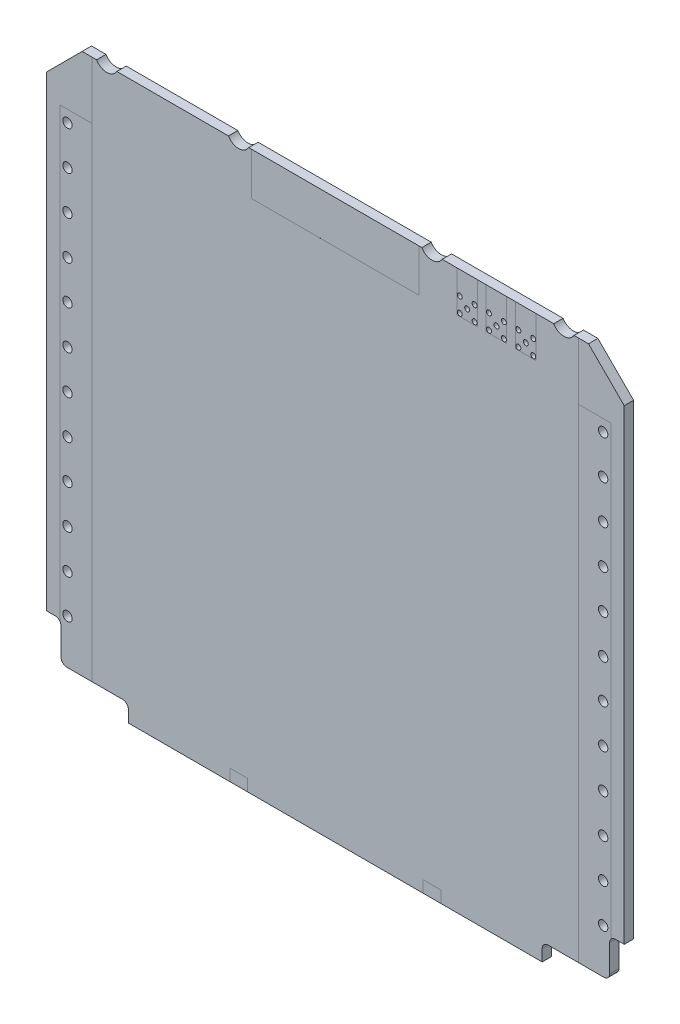
SolidWorks part; units mm, degrees
material "FR4_stuffedProtoboard"
ref_plane "Front Plane" through (0, 0, 0) normal (0, 0, 1) x (1, 0, 0)
ref_plane "Top Plane" through (0, 0, 0) normal (0, 1, 0) x (1, 0, 0)
ref_plane "Right Plane" through (0, 0, 0) normal (1, 0, 0) x (0, 0, -1)
ref_plane "Plane4" through (0, 0, -0.0125) normal (0, 0, -1) x (-1, 0, 0)
sketch "Sketch1" plane through (0, 0, -0.0125) normal (0, 0, -1) x (-1, 0, 0)
  line L4 (49.3, -50) -> (49.3, 45.3)
  line L6 (49.3, 45.3) -> (-49.3, 45.3)
  line L12 (-49.3, 45.3) -> (-49.3, -50)
  line L17 (-49.3, -50) -> (49.3, -50)
  line L18 (0, -50) -> (0, 45.3) construction
  dimension "D7" = 95.3
  dimension "D1" = 98.6
  dimension "D34" = 50
extrude "basicSize" add sketch "Sketch1" against normal blind 1.6
chamfer "Chamfer1" distance 6.1 angle 45 2 edges at (49.3, 45.3, 0.7875) (-49.3, 45.3, 0.7875)
sketch "Sketch4" plane through (0, 0, 1.5875) normal (0, 0, 1) x (1, 0, 0)
  line L1 (37.2679, 45.3) -> (40.7321, 45.3)
  line L7 (-43.2, 45.3) -> (43.2, 45.3) construction
  line L8 (49.3, 39.2) -> (49.3, -50) construction
  arc A0 (40.7321, 45.3) -> (37.2679, 45.3) centre (39, 46.3) cw
  point P5 (39, 44.3)
  dimension "D1" = 2
  dimension "D3" = 10.3
  dimension "D2" = 1
extrude "backplaneSideScrewCutout" cut sketch "Sketch4" against normal through all both and the other way through all
pattern_linear "LPattern3" count 2 spacing 22.5 along (-1, 0, 0) of "backplaneSideScrewCutout"
mirror "Mirror3" about plane through (0, 0, 0) normal (1, 0, 0) of "LPattern3"
sketch "Sketch6" plane through (0, 0, 1.5875) normal (0, 0, 1) x (1, 0, 0)
  line L0 (-49.3, -50) -> (-49.3, 39.2) construction
  line L1 (-49.3, -40.4) -> (-46.8, -40.4)
  line L2 (-49.3, -40.4) -> (-49.3, -50)
  line L4 (-46.8, -40.4) -> (-46.8, -47)
  line L5 (49.3, -50) -> (-49.3, -50) construction
  line L6 (-35.3, -50) -> (-49.3, -50)
  line L7 (-35.3, -50) -> (-35.3, -47)
  line L8 (-35.3, -47) -> (-46.8, -47)
  dimension "D1" = 2.5
  dimension "D2" = 3
  dimension "D3" = 9.6
  dimension "D4" = 14
extrude "Cut-Extrude4" cut sketch "Sketch6" against normal through all
fillet "Fillet1" radius 1 3 edges at (-35.3, -47, 0.7875) (-46.8, -47, 0.7875) (-46.8, -40.4, 0.7875)
mirror "Mirror1" about plane through (0, 0, 0) normal (1, 0, 0) of "Cut-Extrude4", "Fillet1"
sketch "Sketch5" plane through (0, 0, 1.5875) normal (0, 0, 1) x (1, 0, 0)
  line L0 (21.23, 41.37) -> (23.77, 38.83) construction
  line L1 (21.23, 38.83) -> (21.23, 41.37) construction
  line L2 (21.23, 41.37) -> (23.77, 41.37) construction
  line L4 (49.3, 39.2) -> (49.3, -40.4) construction
  line L5 (-14.7679, 45.3) -> (14.7679, 45.3) construction
  circle A0 centre (22.5, 40.1) radius 0.425
  circle A1 centre (21.23, 41.37) radius 0.425
  circle A3 centre (21.23, 38.83) radius 0.425
  circle A4 centre (23.77, 41.37) radius 0.425
  circle A5 centre (23.77, 38.83) radius 0.425
  dimension "D2" = 0.85
  dimension "D1" = 2.54
  dimension "D3" = 3.93
  dimension "D4" = 28.07
extrude "Cut-Extrude3" cut sketch "Sketch5" against normal through all
pattern_linear "LPattern2" count 3 spacing 5 along (1, 0, 0) of "Cut-Extrude3"
sketch "partFootprints" plane through (0, 0, 1.5875) normal (0, 0, 1) x (1, 0, 0)
  line L1 (18.2321, 45.3) -> (37.2679, 45.3) construction
  line L6 (20.75, 45.3) -> (20.75, 38.35)
  line L7 (20.75, 38.35) -> (24.25, 38.35)
  line L8 (24.25, 38.35) -> (24.25, 45.3)
  line L9 (24.25, 45.3) -> (20.75, 45.3)
  line L10 (25.75, 45.3) -> (25.75, 38.35)
  line L11 (25.75, 38.35) -> (29.25, 38.35)
  line L12 (29.25, 38.35) -> (29.25, 45.3)
  line L13 (29.25, 45.3) -> (25.75, 45.3)
  line L14 (30.75, 45.3) -> (30.75, 38.35)
  line L15 (30.75, 38.35) -> (34.25, 38.35)
  line L16 (34.25, 38.35) -> (34.25, 45.3)
  line L17 (34.25, 45.3) -> (30.75, 45.3)
  line L19 (32.5, 38.35) -> (32.5, 40.1) construction
  line L23 (22.5, 38.35) -> (22.5, 40.1) construction
  circle A2 centre (22.5, 40.1) radius 0.425 construction
  circle A5 centre (32.5, 40.1) radius 0.425 construction
  dimension "D1" = 1.75
  dimension "D8" = 3.5
  dimension "D6" = 3
extrude "MMCXfootprint" cut sketch "partFootprints" against normal blind 0.0001
sketch "Sketch7" plane through (0, 0, 1.5875) normal (0, 0, 1) x (1, 0, 0)
  line L0 (-14.2875, 45.5) -> (-14.2875, 39.912) construction
  line L1 (-14.2875, 45.3) -> (-14.2875, 38.007)
  line L2 (-12.2428, 38.007) -> (-11.8872, 38.007) construction
  line L3 (-14.2875, 38.007) -> (14.2875, 38.007)
  line L4 (14.2875, 45.5) -> (14.2875, 39.912) construction
  line L5 (14.2875, 45.3) -> (14.2875, 38.007)
  line L7 (-14.7679, 45.3) -> (14.7679, 45.3) construction
  line L8 (-14.2875, 45.3) -> (14.2875, 45.3)
extrude "TigerEyeFootprint" cut sketch "Sketch7" against normal blind 0.0001
sketch "thermalContacts_upper" plane through (0, 0, 1.5875) normal (0, 0, 1) x (1, 0, 0)
  line L0 (-49.3, -40.4) -> (-49.3, 39.2) construction
  line L1 (35.3, -50) -> (-35.3, -50) construction
  line L2 (-49.3, 45.3) -> (49.3, 45.3) construction
  line L3 (-47, 35.5) -> (-47, -41.5)
  line L5 (-41.5, 35.5) -> (-47, 35.5)
  line L18 (-41.5, 35.5) -> (-41.5, 47)
  line L23 (-41.5, 47) -> (-56.1922, 47)
  line L24 (-56.1922, 47) -> (-56.1922, -41.5)
  line L25 (-56.1922, -41.5) -> (-47, -41.5)
  dimension "D1" = 2.3
  dimension "D2" = 8.5
  dimension "D3" = 9.8
  dimension "D4" = 7.8
  dimension "D5" = 88.5
  dimension "D6" = 14.6922
extrude "keepOut_bottom" cut sketch "thermalContacts_upper" against normal blind 0.0001
sketch "Sketch3" plane through (0, 0, 1.5875) normal (0, 0, 1) x (1, 0, 0)
  line L0 (18.2321, 45.3) -> (20.75, 45.3) construction
  line L1 (-46.8, -46) -> (-46.8, -41.4) construction
  line L2 (-36.3, -47) -> (-45.8, -47) construction
  line L3 (-47, -40.8) -> (-47, 35.5) construction
  line L10 (0, -50) -> (0, 45.3) construction
  line L11 (35.3, -50) -> (-35.3, -50) construction
  line L13 (-41.5, 35.5) -> (-47, 35.5)
  line L14 (-45.8, -47) -> (-41.5, -47)
  line L15 (-46.8, -41.4) -> (-46.8, -46)
  line L16 (-47, 35.5) -> (-47, -40.8)
  line L17 (-41.5, -47) -> (-41.5, 35.5)
  arc A2 (-46.8, -41.4) -> (-47, -40.8) centre (-47.8, -41.4) ccw construction
  arc A3 (-46.8, -46) -> (-45.8, -47) centre (-45.8, -46) ccw construction
  arc A4 (-45.8, -47) -> (-46.8, -46) centre (-45.8, -46) cw
  arc A5 (-47, -40.8) -> (-46.8, -41.4) centre (-47.8, -41.4) cw
extrude "caution_top" cut sketch "Sketch3" against normal blind 0.0001
sketch "hold-downLocations" plane through (0, 0, 1.5875) normal (0, 0, 1) x (1, 0, 0)
  line L0 (-18, -48) -> (-15, -48) construction
  line L1 (-18, -48) -> (-15, -48) construction
  line L2 (15, -48) -> (18, -48) construction
  line L3 (15, -48) -> (18, -48)
  line L4 (18, -48) -> (18, -50)
  line L5 (35.3, -50) -> (-35.3, -50) construction
  line L6 (18, -50) -> (15, -50)
  line L7 (15, -50) -> (15, -48)
  line L8 (-15, -48) -> (-15, -50) construction
  line L9 (-15, -50) -> (-18, -50) construction
  line L10 (-18, -50) -> (-18, -48) construction
extrude "hold-downFootprints" cut sketch "hold-downLocations" against normal blind 0.0001
ref_plane "midplane_Z" through (0, 0, 0.7875) normal (0, 0, 1) x (1, 0, 0)
mirror "clearances_top-bottom" about plane through (0, 0, 0.7875) normal (0, 0, 1) of "hold-downFootprints", "caution_top", "keepOut_bottom"
mirror "clearances_side-side" about plane through (0, 0, 0) normal (1, 0, 0) of "clearances_top-bottom"
sketch "recommendedBuildArea" plane through (0, 0, 1.5875) normal (0, 0, 1) x (1, 0, 0)
  line L0 (41.5, 38.007) -> (41.5, 35.5) construction
  line L1 (-35.3, -45.5) -> (-47, -45.5) construction
  line L2 (-35.3, -47) -> (-35.3, -45.5) construction
  line L3 (35.3, -47) -> (35.3, -45.5) construction
  line L4 (14.2875, 45.3) -> (-14.2875, 45.3)
  line L5 (-14.2875, 45.3) -> (-14.2875, 38.007)
  line L6 (-14.2875, 38.007) -> (14.2875, 38.007)
  line L7 (-43.2, 45.3) -> (-49.3, 39.2)
  line L8 (-49.3, 39.2) -> (-49.3, -40.4)
  line L9 (-49.3, -40.4) -> (-47.8, -40.4)
  line L10 (-47, -40.8) -> (-47, 35.5)
  line L11 (-47, 35.5) -> (-41.5, 35.5)
  line L12 (-41.5, 35.5) -> (-41.5, 45.3)
  line L13 (-41.5, 45.3) -> (-43.2, 45.3)
  line L14 (35.3, -45.5) -> (47, -45.5) construction
  line L15 (38.5, 35.007) -> (38.5, 32.5)
  line L16 (38.5, 32.5) -> (44, 32.5)
  line L17 (-47, -45.5) -> (-47, 35.5) construction
  line L18 (-47, 35.5) -> (-41.5, 35.5) construction
  line L19 (-41.5, 35.5) -> (-41.5, 45.3) construction
  line L20 (44, 32.5) -> (44, -42.5)
  line L21 (14.2875, 38.007) -> (14.2875, 45.3)
  line L22 (32.3, -42.5) -> (44, -42.5)
  line L23 (-14.2875, 45.3) -> (-14.2875, 38.007)
  line L24 (-14.2875, 38.007) -> (41.5, 38.007)
  line L25 (32.3, -47) -> (32.3, -42.5)
  line L26 (32.3, -47) -> (32.3, -47)
  line L27 (21, -47) -> (32.3, -47)
  line L28 (21, -45) -> (21, -47)
  line L29 (41.5, 45.3) -> (41.5, 35.5)
  line L30 (41.5, 35.5) -> (47, 35.5)
  line L31 (47, 35.5) -> (47, -40.8)
  line L32 (47.8, -40.4) -> (49.3, -40.4)
  line L33 (49.3, -40.4) -> (49.3, 39.2)
  line L34 (49.3, 39.2) -> (43.2, 45.3)
  line L35 (43.2, 45.3) -> (41.5, 45.3)
  line L36 (12, -45) -> (21, -45)
  line L37 (41.5, 35.5) -> (47, 35.5) construction
  line L38 (47, 35.5) -> (47, -45.5) construction
  line L39 (12, -47) -> (12, -45)
  line L40 (-12, -47) -> (12, -47)
  line L41 (-12, -45) -> (-12, -47)
  line L42 (-21, -45) -> (-12, -45)
  line L43 (-21, -47) -> (-21, -45)
  line L44 (-32.3, -47) -> (-21, -47)
  line L45 (-32.3, -47) -> (-32.3, -47)
  line L46 (-32.3, -47) -> (-32.3, -42.5)
  line L47 (-32.3, -42.5) -> (-44, -42.5)
  line L48 (-44, -42.5) -> (-44, 32.5)
  line L49 (-44, 32.5) -> (-38.5, 32.5)
  line L50 (-38.5, 32.5) -> (-38.5, 42.3)
  line L51 (-17.2875, 42.3) -> (-38.5, 42.3)
  line L52 (-17.2875, 42.3) -> (-17.2875, 35.007)
  line L53 (-17.2875, 35.007) -> (38.5, 35.007)
  line L72 (-15, -48) -> (-15, -50)
  line L73 (-15, -50) -> (15, -50)
  line L74 (15, -50) -> (15, -48)
  line L75 (15, -48) -> (18, -48)
  line L76 (18, -48) -> (18, -50)
  line L77 (18, -50) -> (35.3, -50)
  line L78 (35.3, -50) -> (35.3, -48)
  line L79 (36.3, -47) -> (41.5, -47)
  line L80 (41.5, -47) -> (41.5, 45.3)
  line L81 (41.5, 45.3) -> (40.7321, 45.3)
  line L82 (37.2679, 45.3) -> (34.25, 45.3)
  line L83 (34.25, 45.3) -> (34.25, 38.35)
  line L84 (34.25, 38.35) -> (30.75, 38.35)
  line L85 (30.75, 38.35) -> (30.75, 45.3)
  line L86 (30.75, 45.3) -> (29.25, 45.3)
  line L87 (29.25, 45.3) -> (29.25, 38.35)
  line L88 (29.25, 38.35) -> (25.75, 38.35)
  line L89 (25.75, 38.35) -> (25.75, 45.3)
  line L90 (25.75, 45.3) -> (24.25, 45.3)
  line L91 (24.25, 45.3) -> (24.25, 38.35)
  line L92 (24.25, 38.35) -> (20.75, 38.35)
  line L93 (20.75, 38.35) -> (20.75, 45.3)
  line L94 (20.75, 45.3) -> (18.2321, 45.3)
  line L95 (14.7679, 45.3) -> (14.2875, 45.3)
  line L96 (14.2875, 45.3) -> (14.2875, 38.007)
  line L97 (14.2875, 38.007) -> (-14.2875, 38.007)
  line L98 (-14.2875, 38.007) -> (-14.2875, 45.3)
  line L99 (-14.2875, 45.3) -> (-14.7679, 45.3)
  line L100 (-18.2321, 45.3) -> (-37.2679, 45.3)
  line L101 (-40.7321, 45.3) -> (-41.5, 45.3)
  line L102 (-41.5, 45.3) -> (-41.5, -47)
  line L103 (-41.5, -47) -> (-36.3, -47)
  line L104 (-35.3, -48) -> (-35.3, -50)
  line L105 (-35.3, -50) -> (-18, -50)
  line L106 (-18, -50) -> (-18, -48)
  line L107 (-18, -48) -> (-15, -48)
  line L108 (-15, -48) -> (-15, -50) construction
  line L109 (-15, -50) -> (15, -50) construction
  line L110 (15, -50) -> (15, -48) construction
  line L111 (15, -48) -> (18, -48) construction
  line L112 (18, -48) -> (18, -50) construction
  line L113 (18, -50) -> (35.3, -50) construction
  line L114 (35.3, -50) -> (35.3, -47) construction
  line L115 (35.3, -47) -> (41.5, -47) construction
  line L133 (41.5, 38.007) -> (-14.2875, 38.007)
  line L134 (-14.2875, 38.007) -> (-14.2875, 45.3)
  line L136 (-14.2875, 45.3) -> (-41.5, 45.3) construction
  line L139 (-41.5, -47) -> (-35.3, -47) construction
  line L140 (-35.3, -47) -> (-35.3, -50) construction
  line L141 (-35.3, -50) -> (-18, -50) construction
  line L142 (-18, -50) -> (-18, -48) construction
  line L143 (-18, -48) -> (-15, -48) construction
  arc A1 (-47, -40.8) -> (-47.8, -40.4) centre (-47.8, -41.4) ccw
  arc A3 (47.8, -40.4) -> (47, -40.8) centre (47.8, -41.4) ccw
  arc A10 (36.3, -47) -> (35.3, -48) centre (36.3, -48) ccw
  arc A11 (37.2679, 45.3) -> (40.7321, 45.3) centre (39, 46.3) ccw
  arc A12 (14.7679, 45.3) -> (18.2321, 45.3) centre (16.5, 46.3) ccw
  arc A13 (-18.2321, 45.3) -> (-14.7679, 45.3) centre (-16.5, 46.3) ccw
  arc A14 (-40.7321, 45.3) -> (-37.2679, 45.3) centre (-39, 46.3) ccw
  arc A15 (-35.3, -48) -> (-36.3, -47) centre (-36.3, -48) ccw
  dimension "D5" = 1.5
  dimension "D1" = 0
  dimension "D2" = 0
  dimension "D3" = 0
  dimension "D4" = 0
  dimension "D6" = 3
ref_point "rail midpoint"
sketch "locatorSketch" plane through (0, 0, 1.5875) normal (0, 0, 1) x (1, 0, 0)
  line L0 (-12.2428, 39.531) -> (12.2428, 38.007) construction
  line L1 (12.2428, 39.531) -> (-12.2428, 38.007) construction
  line L4 (-12.2428, 38.261) -> (-12.2428, 38.007)
  line L5 (-11.8872, 38.261) -> (-12.2428, 38.261)
  line L6 (-11.8872, 38.007) -> (-11.8872, 38.261)
  line L7 (-12.2428, 38.007) -> (-11.8872, 38.007)
  line L8 (-12.2428, 38.261) -> (-12.2428, 38.007)
  line L9 (-11.8872, 38.261) -> (-12.2428, 38.261)
  line L10 (-11.8872, 38.007) -> (-11.8872, 38.261)
  line L11 (-12.2428, 38.007) -> (-11.8872, 38.007)
  line L12 (-12.2428, 39.531) -> (-12.2428, 39.277)
  line L13 (-11.8872, 39.531) -> (-12.2428, 39.531)
  line L14 (-11.8872, 39.277) -> (-11.8872, 39.531)
  line L15 (-12.2428, 39.277) -> (-11.8872, 39.277)
  line L16 (-12.2428, 39.531) -> (-12.2428, 39.277)
  line L17 (-11.8872, 39.531) -> (-12.2428, 39.531)
  line L18 (-11.8872, 39.277) -> (-11.8872, 39.531)
  line L19 (-12.2428, 39.277) -> (-11.8872, 39.277)
  line L20 (11.8872, 39.531) -> (11.8872, 39.277)
  line L21 (12.2428, 39.531) -> (11.8872, 39.531)
  line L22 (12.2428, 39.277) -> (12.2428, 39.531)
  line L23 (11.8872, 39.277) -> (12.2428, 39.277)
  line L24 (11.8872, 39.531) -> (11.8872, 39.277)
  line L25 (12.2428, 39.531) -> (11.8872, 39.531)
  line L26 (12.2428, 39.277) -> (12.2428, 39.531)
  line L27 (11.8872, 39.277) -> (12.2428, 39.277)
  line L28 (11.8872, 38.261) -> (11.8872, 38.007)
  line L29 (12.2428, 38.261) -> (11.8872, 38.261)
  line L30 (12.2428, 38.007) -> (12.2428, 38.261)
  line L31 (11.8872, 38.007) -> (12.2428, 38.007)
  line L32 (11.8872, 38.261) -> (11.8872, 38.007)
  line L33 (12.2428, 38.261) -> (11.8872, 38.261)
  line L34 (12.2428, 38.007) -> (12.2428, 38.261)
  line L35 (11.8872, 38.007) -> (12.2428, 38.007)
  dimension "D1" = 0
  dimension "D2" = 0
  dimension "D3" = 0
  dimension "D4" = 0
sketch "Sketch8" plane through (0, 0, 1.5875) normal (0, 0, 1) x (1, 0, 0)
  line L0 (-49.3, -40.4) -> (-47.8, -40.4) construction
  line L1 (-47, 35.5) -> (-41.5, 35.5) construction
  line L2 (-49.3, -40.4) -> (-49.3, 39.2) construction
  circle A0 centre (-45.7, 33.5) radius 0.8
  circle A1 centre (-45.7, 26.8727) radius 0.8
  circle A2 centre (-45.7, 20.2455) radius 0.8
  circle A3 centre (-45.7, 13.6182) radius 0.8
  circle A4 centre (-45.7, 6.9909) radius 0.8
  circle A5 centre (-45.7, 0.3636) radius 0.8
  circle A6 centre (-45.7, -6.2636) radius 0.8
  circle A7 centre (-45.7, -12.8909) radius 0.8
  circle A8 centre (-45.7, -19.5182) radius 0.8
  circle A9 centre (-45.7, -26.1455) radius 0.8
  circle A10 centre (-45.7, -32.7727) radius 0.8
  circle A11 centre (-45.7, -39.4) radius 0.8
  point P3 (0, 0)
  point P25 (-45.3349, -37.2584)
  point P28 (-45.6493, 33.8123)
  dimension "D1" = 1.6
  dimension "D3" = 1
  dimension "D4" = 2
  dimension "D5" = 3.6
  dimension "D2" = 12
extrude "Cut-Extrude5" cut sketch "Sketch8" against normal blind 10
mirror "Mirror4" about plane through (0, 0, 0) normal (1, 0, 0) of "Cut-Extrude5"
